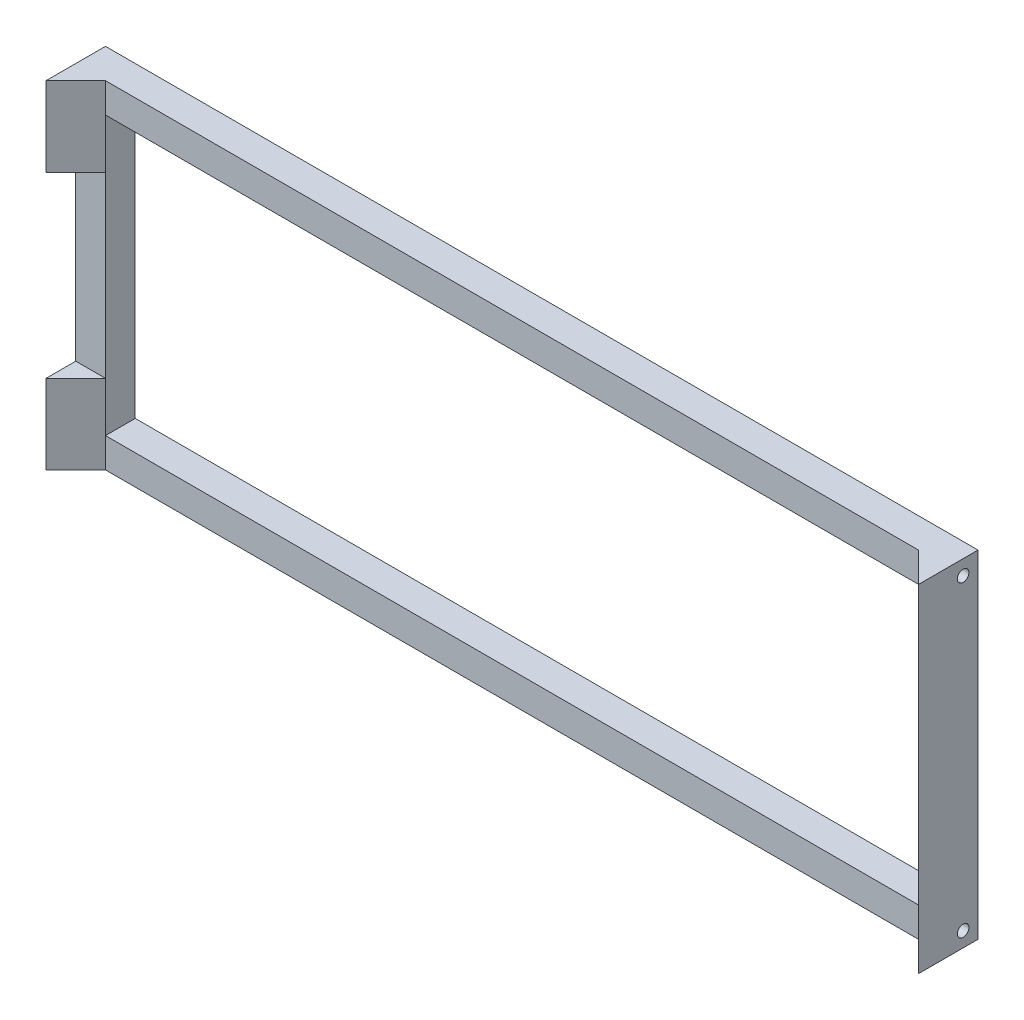
SolidWorks part; units mm, degrees
ref_plane "Front Plane" through (0, 0, 0) normal (1, 0, 0) x (0, 1, 0)
ref_plane "Top Plane" through (0, 0, 0) normal (0, 0, 1) x (0, 1, 0)
ref_plane "Right Plane" through (0, 0, 0) normal (0, 1, 0) x (-1, 0, 0)
sketch "Sketch1" plane through (0, 0, 0) normal (0, 0, 1) x (0, 1, 0)
  line L28 (-42.5, 110) -> (42.5, 110)
  line L29 (-42.5, 110) -> (-42.5, -110)
  line L34 (-42.5, -110) -> (42.5, -110)
  line L35 (42.5, 110) -> (42.5, -110)
  line L50 (-42.5, 110) -> (42.5, -110) construction
  line L55 (-42.5, -110) -> (42.5, 110) construction
  line L64 (-35, 102.5) -> (35, 102.5)
  line L65 (-35, 102.5) -> (-35, -102.5)
  line L70 (-35, -102.5) -> (35, -102.5)
  line L71 (35, 102.5) -> (35, -102.5)
  line L72 (-35, 102.5) -> (35, -102.5) construction
  line L73 (-35, -102.5) -> (35, 102.5) construction
  point P0 (0, 0)
  point P5 (0, 0)
  point P10 (-28.6359, -28.6956)
  point P11 (-81.4868, -84.4385)
  dimension "D1" = 7.5
  dimension "D2" = 7.5
  dimension "D3" = 220
  dimension "D4" = 85
extrude "Boss-Extrude1" add sketch "Sketch1" along normal blind 7.5
sketch "Sketch2" plane through (-110, 0, 0) normal (-1, 0, 0) x (0, -1, 0)
  line L0 (-42.5, 3.75) -> (42.5, 3.75) construction
  line L1 (-42.5, 7.5) -> (-42.5, 0) construction
  line L2 (42.5, 7.5) -> (42.5, 0) construction
  circle A0 centre (-38.75, 3.75) radius 1.45
  circle A1 centre (38.75, 3.75) radius 1.45
  point P10 (0, 0)
  point P11 (0, 0)
  dimension "D1" = 3.75
  dimension "D3" = 2.9
  dimension "D2" = 3.75
extrude "Cut-Extrude1" cut sketch "Sketch2" against normal blind 10
sketch "Sketch3" plane through (110, 0, 0) normal (1, 0, 0) x (0, 1, 0)
  line L0 (-42.5, 3.75) -> (42.5, 3.75) construction
  line L1 (-42.5, 7.5) -> (-42.5, 0) construction
  line L2 (42.5, 7.5) -> (42.5, 0) construction
  circle A0 centre (-38.75, 3.75) radius 1.45
  circle A1 centre (38.75, 3.75) radius 1.45
  dimension "D1" = 3.75
  dimension "D3" = 2.9
  dimension "D2" = 3.75
extrude "Cut-Extrude2" cut sketch "Sketch3" against normal blind 10
sketch "Sketch4" plane through (0, -42.5, 0) normal (0, -1, 0) x (1, 0, 0)
  line L0 (-110, 7.5) -> (-110, 15)
  line L1 (-110, 15) -> (-102.5, 7.5)
  line L2 (-110, 7.5) -> (110, 7.5) construction
  line L3 (-102.5, 7.5) -> (-110, 7.5)
  line L4 (110, 7.5) -> (110, 15)
  line L5 (110, 15) -> (102.5, 7.5)
  line L6 (102.5, 7.5) -> (110, 7.5)
  line M8 (110, 7.5) -> (-110, 7.5)
  dimension "D1" = 7.5
sketch "Sketch5" plane through (0, 42.5, 0) normal (0, 1, 0) x (-1, 0, 0)
  line L0 (-110, 7.5) -> (-110, 15)
  line L1 (-110, 15) -> (-102.5, 7.5)
  line L2 (-110, 7.5) -> (110, 7.5) construction
  line L3 (110, 7.5) -> (110, 15)
  line L4 (110, 15) -> (102.5, 7.5)
  line L5 (102.5, 7.5) -> (110, 7.5)
  line L6 (-110, 7.5) -> (-102.5, 7.5)
  dimension "D1" = 7.5
extrude "Boss-Extrude3" add sketch "Sketch5" against normal through all contours L1 L6 L0
extrude "Boss-Extrude4" add sketch "Sketch5<4>" against normal blind 20 contours L3 L4 L5
sketch "Sketch5<4>" plane through (0, 42.5, 0) normal (0, 1, 0) x (-1, 0, 0) same geometry as "Sketch5"
extrude "Boss-Extrude5" add sketch "Sketch4" against normal blind 20 contours L1 L0 M8 region at (-107.5, -42.5, 10)
